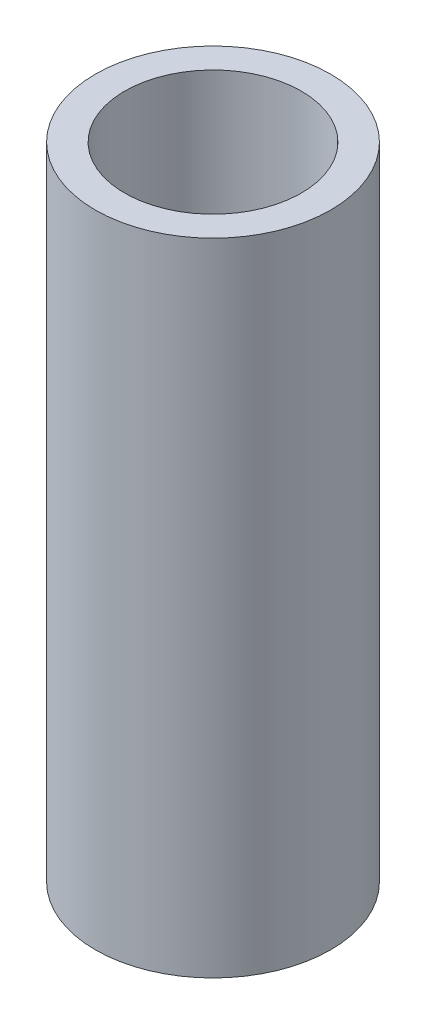
SolidWorks part; units mm, degrees
ref_plane "Front Plane" through (0, 0, 0) normal (0, 0, 1) x (1, 0, 0)
ref_plane "Top Plane" through (0, 0, 0) normal (0, 1, 0) x (1, 0, 0)
ref_plane "Right Plane" through (0, 0, 0) normal (1, 0, 0) x (0, 0, -1)
sketch "Sketch1" plane through (0, 0, 0) normal (0, 1, 0) x (1, 0, 0)
  circle A0 centre (0, 0) radius 20
  dimension "SLEEVE_OD" = 40
extrude "Boss-Extrude1" add sketch "Sketch1" along normal blind 108.8821
sketch "Sketch2" plane through (0, 0, 0) normal (0, 1, 0) x (1, 0, 0)
  circle A0 centre (0, 0) radius 15.0165
  dimension "BORE_D" = 30.0329
extrude "Cut-Extrude1" cut sketch "Sketch2" along normal through all
chamfer "Chamfer1" distance 3.3319 angle 45 rebuild error yes
